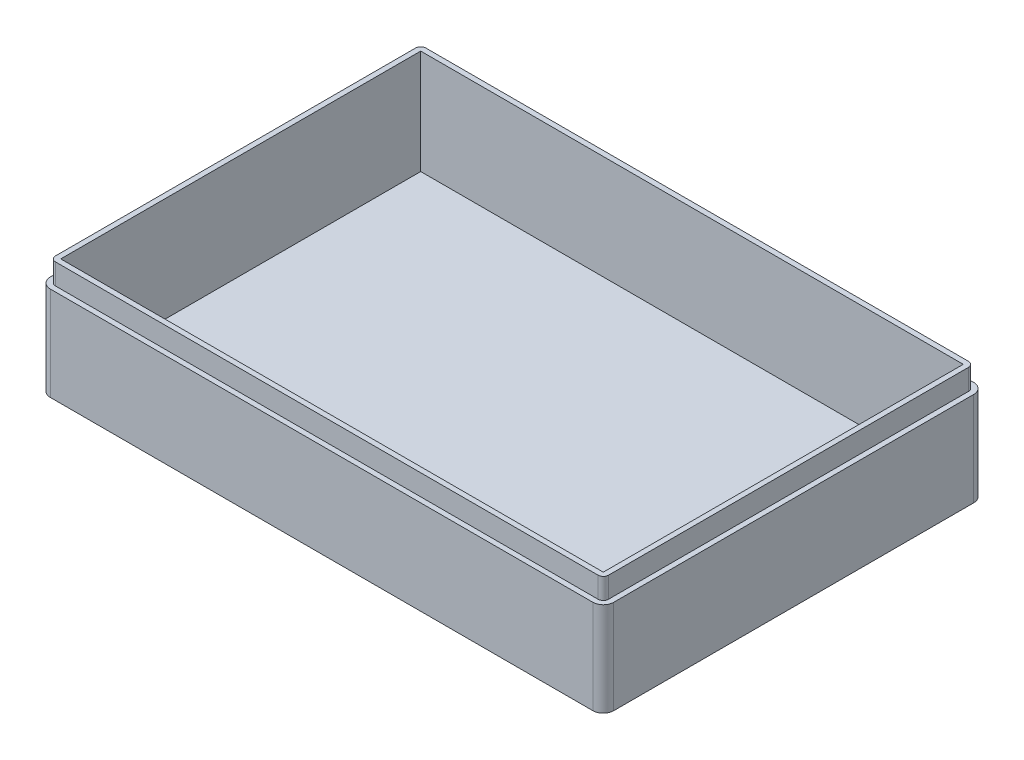
SolidWorks part; units mm, degrees
ref_plane "Front Plane" through (0, 0, 0) normal (0, 0, 1) x (1, 0, 0)
ref_plane "Top Plane" through (0, 0, 0) normal (0, 1, 0) x (1, 0, 0)
ref_plane "Right Plane" through (0, 0, 0) normal (1, 0, 0) x (0, 0, -1)
sketch "Sketch1" plane through (0, 0, 0) normal (0, 1, 0) x (1, 0, 0)
  line L1 (-54, 36.5) -> (54, 36.5)
  line L2 (-54, 36.5) -> (-54, -36.5)
  line L3 (-54, -36.5) -> (54, -36.5)
  line L4 (54, 36.5) -> (54, -36.5)
  line L5 (-54, 36.5) -> (54, -36.5) construction
  line L6 (-54, -36.5) -> (54, 36.5) construction
  point P0 (0, 0)
  dimension "D1" = 108
  dimension "D2" = 73
extrude "Boss-Extrude1" add sketch "Sketch1" along normal blind 22
fillet "Fillet1" radius 2 4 edges at (-54, 11, -36.5) (54, 11, -36.5) (54, 11, 36.5) (-54, 11, 36.5)
shell "Shell1" thickness 2 removed face at (0, 22, 0)
sketch "Sketch6" plane through (0, 22, 0) normal (0, 1, 0) x (1, 0, 0)
  line L8 (53, -34.5) -> (53, 34.5)
  line L9 (52, 35.5) -> (-52, 35.5)
  line L10 (-53, 34.5) -> (-53, -34.5)
  line L11 (-52, -35.5) -> (52, -35.5)
  line L12 (53, -34.5) -> (53, 34.5)
  line L13 (52, 35.5) -> (-52, 35.5)
  line L14 (-53, 34.5) -> (-53, -34.5)
  line L15 (-52, -35.5) -> (52, -35.5)
  arc A4 (-52, 35.5) -> (-53, 34.5) centre (-52, 34.5) ccw
  arc A5 (-52, 35.5) -> (-53, 34.5) centre (-52, 34.5) ccw
  arc A6 (-53, -34.5) -> (-52, -35.5) centre (-52, -34.5) ccw
  arc A7 (-53, -34.5) -> (-52, -35.5) centre (-52, -34.5) ccw
  arc A8 (52, -35.5) -> (53, -34.5) centre (52, -34.5) ccw
  arc A9 (52, -35.5) -> (53, -34.5) centre (52, -34.5) ccw
  arc A10 (53, 34.5) -> (52, 35.5) centre (52, 34.5) ccw
  arc A11 (53, 34.5) -> (52, 35.5) centre (52, 34.5) ccw
  dimension "D1" = 1
extrude "Cut-Extrude5" cut sketch "Sketch6" against normal blind 4 flip side to cut
